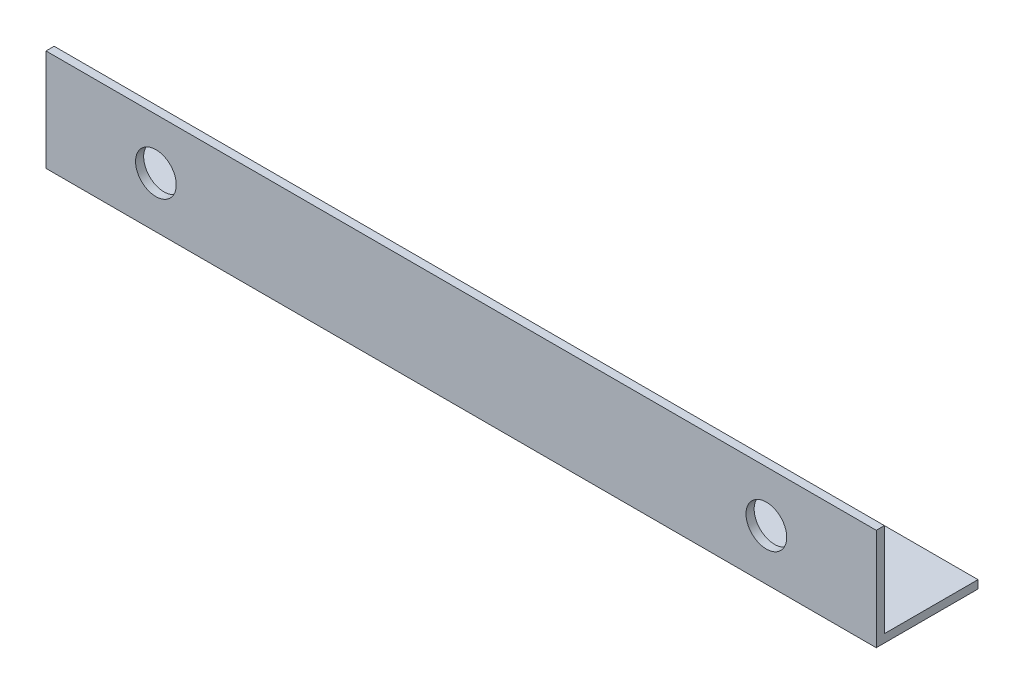
SolidWorks part; units mm, degrees
ref_plane "Спереди" through (0, 0, 0) normal (0, 0, 1) x (1, 0, 0)
ref_plane "Сверху" through (0, 0, 0) normal (0, 1, 0) x (1, 0, 0)
ref_plane "Справа" through (0, 0, 0) normal (1, 0, 0) x (0, 0, -1)
sketch "Эскиз1" plane through (0, 0, 0) normal (1, 0, 0) x (0, 0, -1)
  line L0 (0, 25) -> (0, 0)
  line L1 (0, 0) -> (25, 0)
extrude "Вытянуть-Тонкостенный1" add sketch "Эскиз1" along normal blind 204 thin thin type one direction reverse wall 2
sketch "Эскиз2" plane through (0, 0, 0) normal (0, 0, 1) x (1, 0, 0)
  line L0 (102, 0) -> (102, -9.5468) construction
  line L1 (204, 0) -> (0, 0) construction
  circle A0 centre (27, 12.5) radius 5
  circle A1 centre (177, 12.5) radius 5
extrude "Вырез-Вытянуть1" cut sketch "Эскиз2" against normal through all
